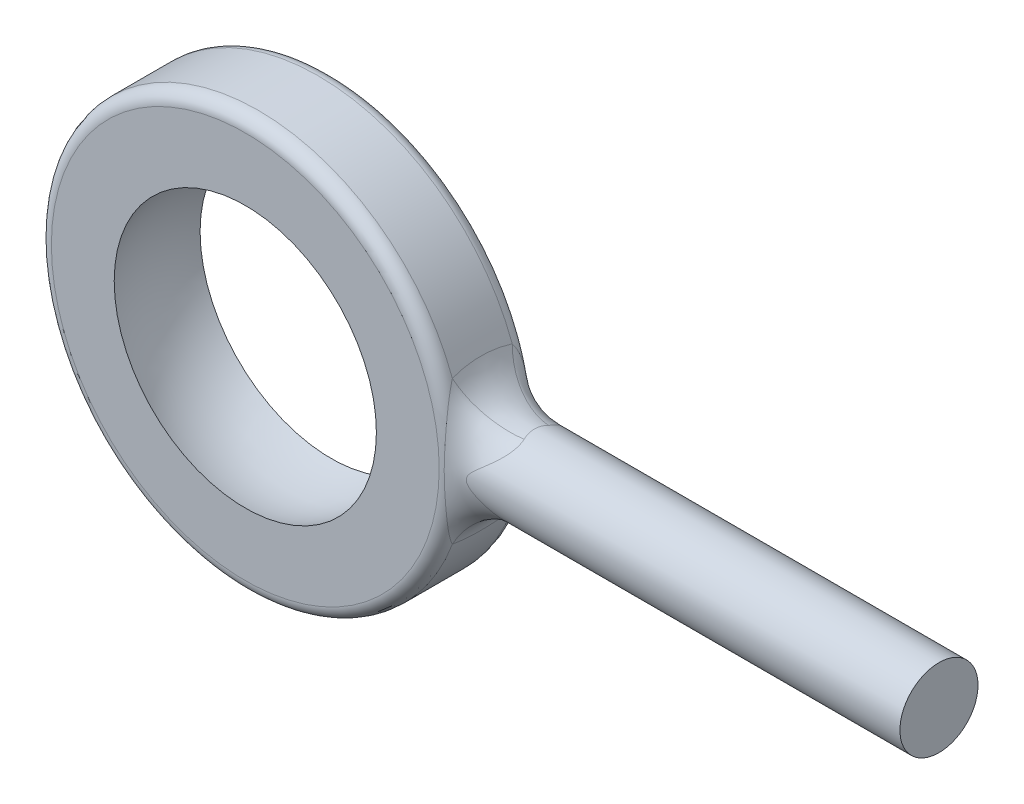
SolidWorks part; units mm, degrees
ref_plane "Front Plane" through (0, 0, 0) normal (0, 0, 1) x (1, 0, 0)
ref_plane "Top Plane" through (0, 0, 0) normal (0, 1, 0) x (1, 0, 0)
ref_plane "Right Plane" through (0, 0, 0) normal (1, 0, 0) x (0, 0, -1)
sketch "Sketch1" plane through (0, 0, 0) normal (0, 0, 1) x (1, 0, 0)
  circle A0 centre (0, 0) radius 15.9
  dimension "D1" = 31.8
extrude "Boss-Extrude1" add sketch "Sketch1" along normal mid plane 6.6
fillet "Fillet1" radius 1 2 edges at (15.9, 0, -3.3) (15.9, 0, 3.3)
sketch "Sketch2" plane through (0, 0, 0) normal (0, 0, 1) x (1, 0, 0)
  line L0 (-10.6, 0) -> (10.6, 0)
  arc A0 (10.6, 0) -> (-10.6, 0) centre (0, 0) ccw
  dimension "D1" = 10.6
revolve "Cut-Revolve1" cut sketch "Sketch2" angle 360 about L0
ref_plane "Plane1" through (50, 0, 0) normal (1, 0, 0) x (0, 0, -1)
sketch "Sketch3" plane through (50, 0, 0) normal (1, 0, 0) x (0, 0, -1)
  circle A0 centre (0, 0) radius 3
  dimension "D1" = 6
extrude "Boss-Extrude2" add sketch "Sketch3" against normal up to next
cosmetic thread "Cosmetic Thread1" parameters "D1"=27, "D2"=5.891
fillet "Fillet2" radius 4.4167 4 edges at (15.6306, 0.3593, -2.9784) (15.6145, -2.9996, 0.051) (15.6306, -0.3593, 2.9784) (15.6292, 2.922, -0.6796)
equation "\"shaft inner diameter\"= 15mm "
equation "\"shaft outer diameter\"= 20mm "
equation "\"column angle\" = 45deg "
equation "\"keyway_height\" = 1.39mm "
equation "\"keyway_width\" = 2.78mm "
equation "\"keyway_length\" = 30mm "
equation "\"steering column length\" = 555mm "
equation "\"steering wheel bolt width\" = 6mm "
equation "\"steering wheel bolt length\" = 40mm "
equation "\"bushing length\" = 40mm "
equation "\"bushing thickness\" = 3mm "
equation "\"u_joint clearance\" = 30mm "
equation "\"u_joint thickness\" = 7.5mm "
equation "\"horizontal shaft length\" = 90mm "
equation "\"short_bearing_outer_width\" = 10mm "
equation "\"column bushing diameter\" = \"primary shaft small diameter\" + 4 "
equation "\"column bushing distance\" = \"steering column length\"/4 "
equation "\"pinion width\" = 26.5mm "
equation "\"pin hole diameter\" = 10mm "
equation "\"rack hole to hole\" = 500mm "
equation "\"rack length\" = \"rack hole to hole\" + \"pin hole diameter\"*2 "
equation "\"rack height\"= \"pin hole diameter\" * 2mm"
equation "\"pitch diameter\" = \"max travel\"/(pi * \"turn to lock\") "
equation "\"number of teeth\" = 18mm "
equation "\"module\" = \"pitch diameter\" / \"number of teeth\" "
equation "\"pressure angle\" = 20deg "
equation "\"D1@Boss-Extrude1\"=\"tie rod inner diameter\""
equation "\"wheel base\" = 1561mm "
equation "\"track\" = 1354mm "
equation "\"turning radius\" = 2000mm "
equation "\"steering arm length\" = 100mm "
equation "\"turn to lock\" = 0.75mm "
equation "\"D1@Fillet2\"=\"pinion width\"/6"
equation "\"D1@Sketch1\"=\"pinion width\"*1.2"
equation "\"D1@Sketch2\"=\"pinion width\"/2.5"
equation "\"max turning angle\" = atn(\"wheel base\" / (\"turning radius\" - 0.5 * \"track\")) "
equation "\"max travel\" = 2 * \"steering arm length\" * sin(0.5 * \"max turning angle\") "
equation "\"primary shaft small diameter\" = 16mm "
equation "\"primary shaft large diameter\" = 24mm "
equation "\"secondary shaft small diameter\" = 16mm "
equation "\"secondary shaft large diameter\" = 25mm "
equation "\"tie rod length\" = 305mm "
equation "\"tie rod inner diameter\" = 6.6mm "
equation "\"tie rod outer diameter\" = 8.1mm "
equation "\"D1@Sketch3\"=\"tie rod inner diameter\"-0.6"
